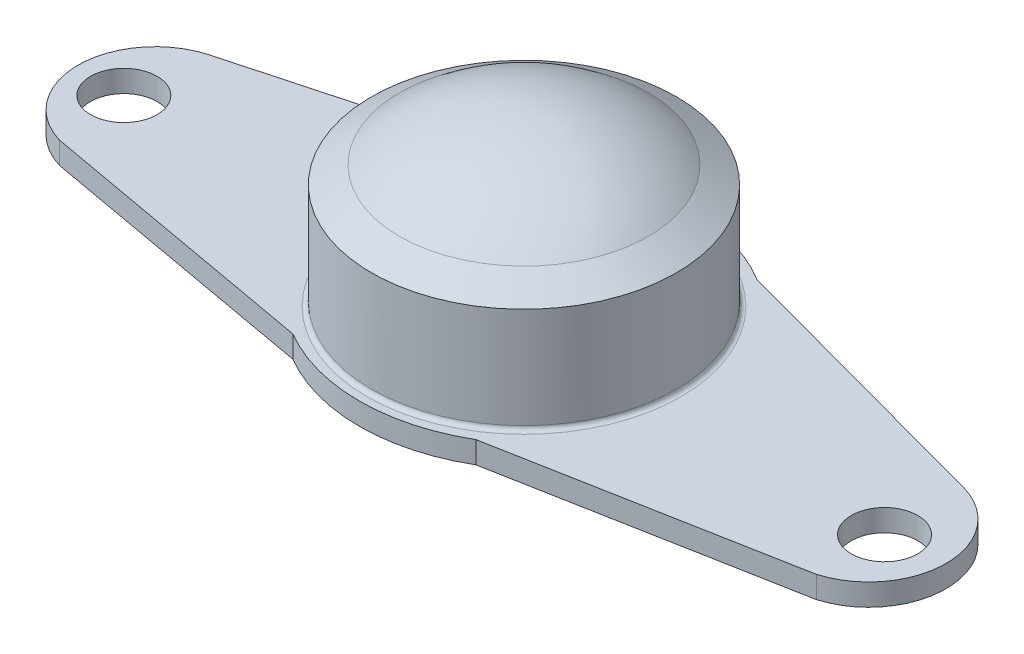
SolidWorks part; units mm, degrees
ref_plane "Front Plane" through (0, 0, 0) normal (0, 0, 1) x (1, 0, 0)
ref_plane "Top Plane" through (0, 0, 0) normal (0, 1, 0) x (1, 0, 0)
ref_plane "Right Plane" through (0, 0, 0) normal (1, 0, 0) x (0, 0, -1)
sketch "Sketch2" plane through (0, 0, 0) normal (0, 1, 0) x (1, 0, 0)
  line L0 (-67.606, 27.3895) -> (-35.298, 36.1464)
  line L1 (-67.7838, 10.4095) -> (-35.298, 4.5678)
  line L5 (18.3298, 10.6789) -> (-14.4229, 4.5678)
  line L6 (18.1519, 27.6589) -> (-14.1561, 36.4158)
  arc A0 (-67.606, 27.3895) -> (-67.7838, 10.4095) centre (-65.298, 18.8744) ccw
  arc A1 (-14.1561, 36.4158) -> (-35.298, 36.1464) centre (-24.5138, 19.5458) ccw
  arc A2 (-14.4229, 4.5678) -> (-35.298, 4.5678) centre (-24.8605, 22.328) cw
  arc A3 (18.1519, 27.6589) -> (16.4628, 10.3432) centre (15.8439, 19.1438) cw
extrude "Boss-Extrude2" add sketch "Sketch2" along normal blind 2.5 contours A3 L6 A1 L0 A0 L1 A2 L5 region at (-24.6948, 0, -19.9634)
sketch "Sketch3" plane through (0, 2.5, 0) normal (0, 1, 0) x (1, 0, 0)
  circle A0 centre (-24.8479, 20.4954) radius 17.4037
extrude "Boss-Extrude3" add sketch "Sketch3" along normal blind 14
chamfer "Chamfer1" distance 2 angle 58 1 edges at (-24.8479, 16.5, -3.0917) first distance on face at (-24.8479, 16.5, -3.0917)
dome "Dome1" faces to dome 1 distance 5.08 reverse direction no elliptical dome no face at (-24.8479, 16.5, -6.2924) parameters "D1"=5.08
sketch "Sketch4" plane through (0, 2.5, 0) normal (0, 1, 0) x (1, 0, 0)
  circle A0 centre (18.3035, 18.4933) radius 3.7942
  circle A1 centre (-68.51, 18.4933) radius 3.7942
  dimension "D1" = 7.5883
  dimension "D2" = 7.5883
extrude "Cut-Extrude1" cut sketch "Sketch4" against normal blind 22.225
fillet "Fillet1" radius 0.5 1 edges at (-24.8479, 2.5, -3.0917)
